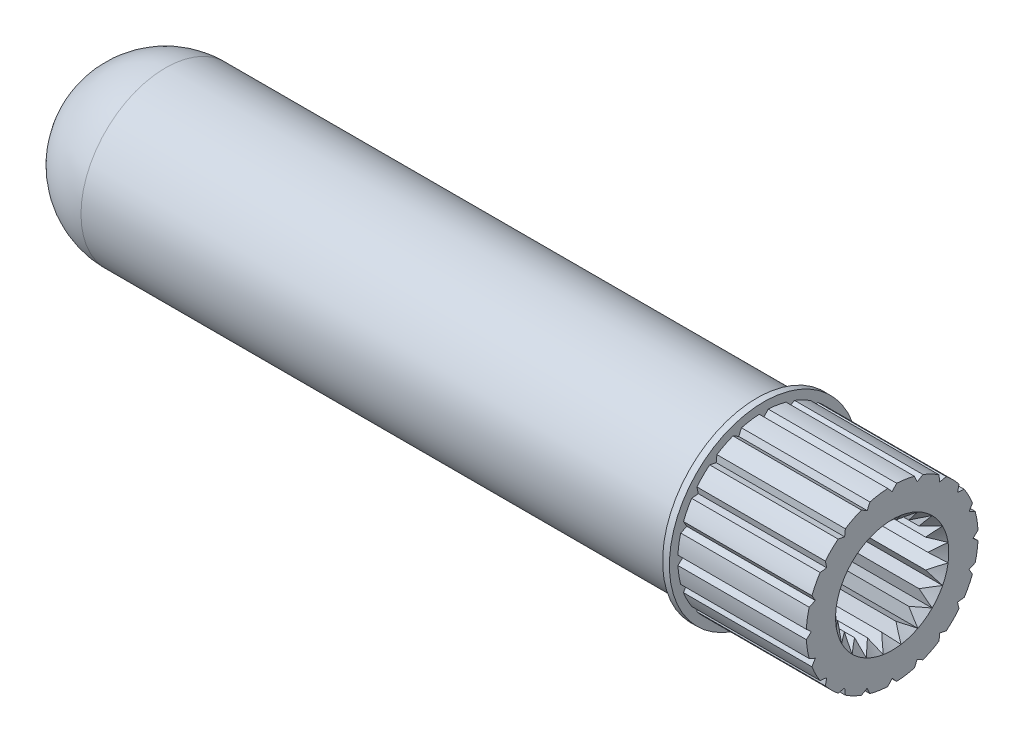
SolidWorks part; units mm, degrees
other "Markup1"
sketch "Sketch46" [suppressed] plane through (18, -9.875, -10) normal (1, 0, 0) x (0, 0, -1)
other "Markup2"
sketch "Sketch47" [suppressed] plane through (18, 5.325, 10) normal (0.9757, 0.2179, 0.0233) x (0.0219, 0.009, -0.9997)
other "DetailItem1"
ref_plane "Front Plane" through (0, 0, 0) normal (0, 0, 1) x (1, 0, 0)
ref_plane "Top Plane" through (0, 0, 0) normal (0, 1, 0) x (1, 0, 0)
ref_plane "Right Plane" through (0, 0, 0) normal (1, 0, 0) x (0, 0, -1)
sketch "Sketch1" plane through (0, 0, 0) normal (0, 1, 0) x (1, 0, 0)
  line L1 (-10, 10) -> (10, 10)
  line L2 (-10, 10) -> (-10, -10)
  line L3 (-10, -10) -> (10, -10)
  line L4 (10, 10) -> (10, -10)
  line L5 (-10, 10) -> (10, -10) construction
  line L6 (-10, -10) -> (10, 10) construction
  point P0 (0, 0)
  dimension "D1" = 20
extrude "Boss-Extrude1" add sketch "Sketch1" along normal blind 5.325 and the other way blind 15.3125
sketch "Sketch2" plane through (0, 0, 0) normal (0, 1, 0) x (1, 0, 0)
  line L0 (0, 0) -> (20, 0)
  dimension "D1" = 20
sketch "Sketch3" plane through (0, 5.325, 0) normal (0, 1, 0) x (1, 0, 0)
  circle A0 centre (0, 0) radius 7.575
  dimension "D1" = 15.15
extrude "Cut-Extrude1" cut sketch "Sketch3" against normal blind 4.3
sketch "Sketch4" plane through (0, 5.325, 0) normal (0, 1, 0) x (1, 0, 0)
  circle A0 centre (0, 0) radius 7
  dimension "D1" = 14
extrude "Cut-Extrude2" cut sketch "Sketch4" against normal blind 12
sketch "Sketch5" plane through (0, 5.325, 0) normal (0, 1, 0) x (1, 0, 0)
  circle A0 centre (0, 0) radius 3.45
  dimension "D1" = 6.9
extrude "Cut-Extrude3" cut sketch "Sketch5" against normal blind 15.2
sketch "Sketch6" plane through (0, 5.325, 0) normal (0, 1, 0) x (1, 0, 0)
  line L4 (10, -10) -> (10, 10)
  line L5 (10, 10) -> (-10, 10)
  line L6 (-10, 10) -> (-10, -10)
  line L7 (-10, -10) -> (10, -10)
  line L8 (10, -10) -> (10, 10)
  line L9 (10, 10) -> (-10, 10)
  line L10 (-10, 10) -> (-10, -10)
  line L11 (-10, -10) -> (10, -10)
  circle A0 centre (0, 0) radius 9 construction
  dimension "D1" = 18
  dimension "D2" = 0
extrude "Cut-Extrude4" cut sketch "Sketch6" against normal through all from offset 15.2 offset against normal yes
sketch "Sketch7" [suppressed] plane through (0, -9.875, 0) normal (0, -1, 0) x (1, 0, 0)
  line L0 (-10, -10) -> (-10, 10) construction
  line L1 (-15.4242, -7.75) -> (-4.5758, -7.75)
  line L2 (-15.4242, -7.75) -> (-15.4242, 7.75)
  line L3 (-15.4242, 7.75) -> (-4.5758, 7.75)
  line L4 (-4.5758, -7.75) -> (-4.5758, 7.75)
  line L5 (-15.4242, -7.75) -> (-4.5758, 7.75) construction
  line L6 (-15.4242, 7.75) -> (-4.5758, -7.75) construction
  circle A0 centre (0, 0) radius 9 construction
  point P0 (-10, 0)
  dimension "D1" = 15.5
extrude "Cut-Extrude7" [suppressed] cut sketch "Sketch7" along normal through all
sketch "Sketch10" plane through (0, -9.875, 0) normal (0, -1, 0) x (1, 0, 0)
  line L1 (-1.4, -7) -> (1.4, -7)
  line L2 (-1.4, -7) -> (-1.4, -9)
  line L3 (-1.4, -9) -> (1.4, -9)
  line L4 (1.4, -7) -> (1.4, -9)
  line L5 (-1.4, -7) -> (1.4, -9) construction
  line L6 (-1.4, -9) -> (1.4, -7) construction
  point P3 (0, -8)
  dimension "D1" = 2.8
  dimension "D2" = 2
  dimension "D3" = 8
extrude "Cut-Extrude9" cut sketch "Sketch10" against normal blind 3
sketch "Sketch15" plane through (0, 5.325, 0) normal (0, 1, 0) x (1, 0, 0)
  line L0 (-6.8653, 3.2013) -> (-7.725, 1.3577)
  line L1 (-7.725, 1.3577) -> (-7.725, -1.3577)
  line L2 (-7.725, -1.3577) -> (-6.8653, -3.2013)
  line L3 (-6.8653, -3.2013) -> (-6.8653, 3.2013)
  circle A0 centre (0, 0) radius 7.575 construction
  circle A1 centre (0, 0) radius 7.575 construction
  point P9 (-7.575, 0)
  dimension "D1" = 25
  dimension "D2" = 0.15
extrude "Cut-Extrude11" cut sketch "Sketch15" against normal up to surface (4.3 mm away) up to face at (0, 1.025, 7)
sketch "Sketch16" plane through (0, -6.675, 0) normal (0, 1, 0) x (1, 0, 0)
  line L0 (-3.1268, 1.458) -> (-3.6, 0.4432)
  line L1 (-3.6, 0.4432) -> (-3.6, -0.4432)
  line L2 (-3.6, -0.4432) -> (-3.1268, -1.458)
  line L3 (-3.1268, -1.458) -> (-3.1268, 1.458)
  circle A0 centre (0, 0) radius 3.45 construction
  point P6 (-3.45, 0)
  dimension "D1" = 0.15
  dimension "D2" = 25
extrude "Cut-Extrude12" cut sketch "Sketch16" against normal up to surface (3.2 mm away) up to face at (0, -9.875, -8)
fillet "Fillet1" radius 10 2 edges at (-10, -2.275, -10) (-10, -2.275, 10)
chamfer "Chamfer5" distance 1 angle 45 4 edges at (5, 5.325, -10) (-7.0711, 5.325, -7.0711) (5, 5.325, 10) (-7.0711, 5.325, 7.0711)
sketch "Sketch18" plane through (10, 0, 0) normal (1, 0, 0) x (0, 0, -1)
  line L0 (-10, -9.875) -> (-10, 4.325) construction
  circle A0 centre (0, 0) radius 10
extrude "Cut-Extrude14" cut sketch "Sketch18" against normal blind 5 flip side to cut
sketch "Sketch19" plane through (5, 0, 0) normal (1, 0, 0) x (0, 0, -1)
  circle A1 centre (0, 0) radius 10
  circle A2 centre (0, 0) radius 10
  dimension "D1" = 0
extrude "Cut-Extrude15" cut sketch "Sketch19" against normal blind 5 draft 60 flip side to cut
sketch "Sketch8" plane through (10, 0, 0) normal (1, 0, 0) x (0, 0, -1)
  circle A0 centre (0, 0) radius 3.35
  dimension "D1" = 6.7
extrude "Start side connector" cut sketch "Sketch8" against normal blind 1.8
sketch "Sketch38" [suppressed] plane through (0, 5.325, 0) normal (0, 1, 0) x (1, 0, 0)
  line L0 (0, -10) -> (10, -10) construction
  line L4 (20, 10) -> (20, -10)
  line L9 (0, 10) -> (0, 15)
  line L10 (0, 15) -> (20, 15)
  line L11 (20, 15) -> (20, 10)
  line L12 (0, -10) -> (0, -15)
  line L13 (0, -15) -> (20, -15)
  line L14 (20, -15) -> (20, -10)
  arc A0 (0, 10) -> (9.5394, -3) centre (0, 0) cw
  arc A1 (0, 10) -> (0, -10) centre (0, 0) ccw construction
  arc A2 (9.5394, -3) -> (0, -10) centre (0, 0) cw
extrude "Cut-Extrude27" [suppressed] cut sketch "Sketch38" against normal through all draft 30
sketch "Sketch9" plane through (10, 0, 0) normal (1, 0, 0) x (0, 0, -1)
  circle A0 centre (0, 0) radius 3.35 construction
  circle A1 centre (0, 0) radius 3.35
  circle A2 centre (0, 0) radius 5.085
  dimension "D1" = 10.17
extrude "Boss-Extrude2" add sketch "Sketch9" along normal blind 8
sketch "Sketch40" plane through (10, 0, 0) normal (1, 0, 0) x (0, 0, -1)
  circle A0 centre (0, 0) radius 5.085 construction
  circle A1 centre (0, 0) radius 5.085
  circle A2 centre (0, 0) radius 5.585
  dimension "D1" = 0.5
extrude "Boss-Extrude10" add sketch "Sketch40" along normal blind 0.4 and the other way blind 1
sketch "Sketch41" [suppressed] plane through (9, 0, 0) normal (-1, 0, 0) x (0, 0, 1)
  line L1 (-1.6842, 5.325) -> (1.6842, 5.325)
  line L2 (-1.6842, 5.325) -> (1.6842, 5.325)
  arc A1 (1.6842, 5.325) -> (-1.6842, 5.325) centre (0, 0) ccw
  arc A2 (1.6842, 5.325) -> (-1.6842, 5.325) centre (0, 0) ccw
  dimension "D1" = 0
extrude "Cut-Extrude28" [suppressed] cut sketch "Sketch41" against normal through all
sketch "Sketch12" plane through (18, 0, 0) normal (1, 0, 0) x (0, 0, -1)
  line L0 (-0.5241, -3.3088) -> (0, -2.73)
  line L1 (0, -2.73) -> (0.5241, -3.3088)
  line L2 (-0.5241, -3.3088) -> (0, 0) construction
  line L3 (0, 0) -> (0.5241, -3.3088) construction
  circle A3 centre (0, 0) radius 3.35 construction
  arc A4 (-0.5241, -3.3088) -> (0.5241, -3.3088) centre (0, 0) ccw
  point P5 (0, -3.35)
  dimension "D1" = 18
  dimension "D2" = 0.62
extrude "Boss-Extrude4" add sketch "Sketch12" against normal up to surface (9.8 mm away) up to face at (8.2, 0, -3.35)
sketch "Sketch17" plane through (18, 0, 0) normal (1, 0, 0) x (0, 0, -1)
  line L0 (-0.2654, -5.0781) -> (0, -4.785)
  line L1 (0, -4.785) -> (0.2654, -5.0781)
  line L2 (0, -2.73) -> (0.5241, -3.3088) construction
  line L3 (-0.5241, -3.3088) -> (0, -2.73) construction
  circle A0 centre (0, 0) radius 5.085 construction
  circle A1 centre (0, 0) radius 5.085 construction
  arc A2 (-0.2654, -5.0781) -> (0.2654, -5.0781) centre (0, 0) ccw
  point P7 (0, -5.085)
  dimension "D1" = 0.3
extrude "Cut-Extrude13" cut sketch "Sketch17" against normal up to surface (7.6 mm away) up to face at (10.4, 0, -5.585)
pattern_circular "CirPattern1" count 20 over 360 about axis through (8.2, 0, 0) along (1, 0, 0) of "Boss-Extrude4", "Cut-Extrude13" reverse direction yes
sketch "Sketch14" plane through (0, 0, 0) normal (0, 1, 0) x (1, 0, 0)
  line L0 (18, 2.35) -> (18, 3.35)
  line L1 (18, -5.085) -> (18, 5.085) construction
  line L2 (18, 3.35) -> (17, 2.35)
  line L3 (17, 2.35) -> (18, 2.35)
  line L8 (10, -3.35) -> (10, 3.35) construction
  point P13 (10, 3.35)
  dimension "D1" = 45
  dimension "D3" = 1
revolve "Cut-Revolve1" cut sketch "Sketch14" angle 360 about L0
fillet "Fillet2" [suppressed] radius 2
chamfer "Chamfer7" [suppressed] distance 4.4 angle 30
sketch "Sketch21" [suppressed] plane through (10, 0, 0) normal (1, 0, 0) x (0, 0, -1)
  circle A0 centre (0, 0) radius 3.55
  circle A1 centre (0, 0) radius 5.15
  dimension "D1" = 7.1
  dimension "D2" = 1.6
extrude "Boss-Extrude5" [suppressed] add sketch "Sketch21" along normal blind 10
sketch "Sketch22" [suppressed] plane through (0, 0, 0) normal (0, 0, 1) x (1, 0, 0)
  line L1 (10, 0) -> (20, 0) construction
  line L2 (10, -5.15) -> (10, 5.15) construction
  line L3 (20, -5.15) -> (20, 5.15) construction
  circle A0 centre (15, 0) radius 1
  dimension "D1" = 2
extrude "Cut-Extrude16" [suppressed] cut sketch "Sketch22" against normal through all both and the other way through all
chamfer "Chamfer3" [suppressed] distance 5 angle 45
sketch "Sketch23" [suppressed] plane through (10, 0, 0) normal (1, 0, 0) x (0, 0, -1)
  circle A0 centre (0, 0) radius 20
  dimension "D1" = 40
extrude "Cut-Extrude17" [suppressed] cut sketch "Sketch23" against normal through all
sketch "Sketch24" [suppressed] plane through (10, 0, 0) normal (-1, 0, 0) x (0, 0, 1)
  circle A0 centre (0, 0) radius 3.55
  circle A1 centre (0, 0) radius 6
  circle A2 centre (0, 0) radius 5.085 construction
  dimension "D1" = 7.1
  dimension "D2" = 2.45
  dimension "D3" = 12
extrude "Boss-Extrude6" [suppressed] add sketch "Sketch24" along normal blind 10
sketch "Sketch26" [suppressed] plane through (10, 0, 0) normal (1, 0, 0) x (0, 0, -1)
  circle A0 centre (0, 0) radius 9
  circle A1 centre (0, 0) radius 6 construction
  circle A2 centre (0, 0) radius 6
  dimension "D1" = 18
extrude "Boss-Extrude7" [suppressed] add sketch "Sketch26" against normal blind 3
chamfer "Chamfer1" [suppressed] distance 3 angle 45
sketch "Sketch25" [suppressed] plane through (0, 0, 0) normal (0, 1, 0) x (1, 0, 0)
  circle A0 centre (4, 0) radius 1
  dimension "D1" = 2
  dimension "D2" = 4
extrude "Cut-Extrude18" [suppressed] cut sketch "Sketch25" against normal through all both and the other way through all
sketch "Sketch43" plane through (10, 0, 0) normal (1, 0, 0) x (0, 0, -1)
  circle A0 centre (0, 0) radius 20
  dimension "D1" = 40
extrude "Cut-Extrude29" cut sketch "Sketch43" against normal through all
sketch "Sketch44" plane through (10, 0, 0) normal (-1, 0, 0) x (0, 0, 1)
  circle A0 centre (0, 0) radius 5
  dimension "D1" = 10
extrude "Boss-Extrude11" add sketch "Sketch44" along normal blind 40
sketch "Sketch45" plane through (10, 0, 0) normal (-1, 0, 0) x (0, 0, 1)
  circle A0 centre (0, 0) radius 9
  dimension "D1" = 18
extrude "Boss-Extrude12" [suppressed] add sketch "Sketch45" along normal blind 3
chamfer "Chamfer4" [suppressed] distance 4 angle 45
fillet "Fillet4" radius 5 1 edges at (-30, 0, 5)
sketch "Sketch27" [suppressed] plane through (10, 0, 0) normal (1, 0, 0) x (0, 0, -1)
  circle A0 centre (0, 0) radius 20
  dimension "D1" = 40
extrude "Cut-Extrude19" [suppressed] cut sketch "Sketch27" against normal through all
sketch "Sketch28" [suppressed] plane through (10, 0, 0) normal (-1, 0, 0) x (0, 0, 1)
  circle A1 centre (0, 0) radius 9
  dimension "D1" = 18
extrude "Boss-Extrude8" [suppressed] add sketch "Sketch28" along normal blind 10
sketch "Sketch29" [suppressed] plane through (10, 0, 0) normal (1, 0, 0) x (0, 0, -1)
  line L40 (-2.2086, 1.6047) -> (-2.9849, 1.5209)
  line L42 (-2.2086, 1.6047) -> (-2.9849, 1.5209)
  line L44 (-2.9849, 1.5209) -> (-2.5964, 0.8436)
  line L46 (-2.9849, 1.5209) -> (-2.5964, 0.8436)
  line L48 (-2.5964, 0.8436) -> (-3.3088, 0.5241)
  line L50 (-2.5964, 0.8436) -> (-3.3088, 0.5241)
  line L52 (-3.3088, 0.5241) -> (-2.73, 0)
  line L54 (-3.3088, 0.5241) -> (-2.73, 0)
  line L56 (-2.73, 0) -> (-3.3088, -0.5241)
  line L58 (-2.73, 0) -> (-3.3088, -0.5241)
  line L60 (-3.3088, -0.5241) -> (-2.5964, -0.8436)
  line L62 (-3.3088, -0.5241) -> (-2.5964, -0.8436)
  line L64 (-2.5964, -0.8436) -> (-2.9849, -1.5209)
  line L66 (-0.5241, -3.3088) -> (0, -2.73)
  line L67 (-0.5241, -3.3088) -> (0, -2.73)
  line L68 (0, -2.73) -> (0.5241, -3.3088)
  line L69 (0, -2.73) -> (0.5241, -3.3088)
  line L70 (-2.5964, -0.8436) -> (-2.9849, -1.5209)
  line L72 (-2.9849, -1.5209) -> (-2.2086, -1.6047)
  line L74 (-2.9849, -1.5209) -> (-2.2086, -1.6047)
  line L76 (-2.2086, -1.6047) -> (-2.3688, -2.3688)
  line L78 (-2.2086, -1.6047) -> (-2.3688, -2.3688)
  line L120 (-2.3688, -2.3688) -> (-1.6047, -2.2086)
  line L122 (-2.3688, -2.3688) -> (-1.6047, -2.2086)
  line L124 (-1.6047, -2.2086) -> (-1.5209, -2.9849)
  line L126 (-1.6047, -2.2086) -> (-1.5209, -2.9849)
  line L128 (-1.5209, -2.9849) -> (-0.8436, -2.5964)
  line L130 (-1.5209, -2.9849) -> (-0.8436, -2.5964)
  line L132 (-0.8436, -2.5964) -> (-0.5241, -3.3088)
  line L134 (-0.8436, -2.5964) -> (-0.5241, -3.3088)
  line L136 (0.5241, -3.3088) -> (0.8436, -2.5964)
  line L138 (0.5241, -3.3088) -> (0.8436, -2.5964)
  line L140 (0.8436, -2.5964) -> (1.5209, -2.9849)
  line L142 (0.8436, -2.5964) -> (1.5209, -2.9849)
  line L144 (1.5209, -2.9849) -> (1.6047, -2.2086)
  line L146 (1.5209, -2.9849) -> (1.6047, -2.2086)
  line L148 (1.6047, -2.2086) -> (2.3688, -2.3688)
  line L150 (1.6047, -2.2086) -> (2.3688, -2.3688)
  line L152 (2.3688, -2.3688) -> (2.2086, -1.6047)
  line L154 (2.3688, -2.3688) -> (2.2086, -1.6047)
  line L156 (2.2086, -1.6047) -> (2.9849, -1.5209)
  line L158 (2.2086, -1.6047) -> (2.9849, -1.5209)
  line L160 (2.9849, -1.5209) -> (2.5964, -0.8436)
  line L161 (2.9849, -1.5209) -> (2.5964, -0.8436)
  line L162 (2.5964, -0.8436) -> (3.3088, -0.5241)
  line L163 (2.5964, -0.8436) -> (3.3088, -0.5241)
  line L164 (3.3088, -0.5241) -> (2.73, 0)
  line L165 (3.3088, -0.5241) -> (2.73, 0)
  line L166 (2.73, 0) -> (3.3088, 0.5241)
  line L167 (2.73, 0) -> (3.3088, 0.5241)
  line L168 (3.3088, 0.5241) -> (2.5964, 0.8436)
  line L169 (3.3088, 0.5241) -> (2.5964, 0.8436)
  line L170 (2.5964, 0.8436) -> (2.9849, 1.5209)
  line L171 (2.5964, 0.8436) -> (2.9849, 1.5209)
  line L172 (2.9849, 1.5209) -> (2.2086, 1.6047)
  line L173 (2.9849, 1.5209) -> (2.2086, 1.6047)
  line L174 (2.2086, 1.6047) -> (2.3688, 2.3688)
  line L175 (2.2086, 1.6047) -> (2.3688, 2.3688)
  line L176 (2.3688, 2.3688) -> (1.6047, 2.2086)
  line L177 (2.3688, 2.3688) -> (1.6047, 2.2086)
  line L178 (1.6047, 2.2086) -> (1.5209, 2.9849)
  line L179 (1.6047, 2.2086) -> (1.5209, 2.9849)
  line L180 (1.5209, 2.9849) -> (0.8436, 2.5964)
  line L181 (1.5209, 2.9849) -> (0.8436, 2.5964)
  line L182 (0.8436, 2.5964) -> (0.5241, 3.3088)
  line L183 (0.8436, 2.5964) -> (0.5241, 3.3088)
  line L184 (0.5241, 3.3088) -> (0, 2.73)
  line L185 (0.5241, 3.3088) -> (0, 2.73)
  line L186 (0, 2.73) -> (-0.5241, 3.3088)
  line L187 (0, 2.73) -> (-0.5241, 3.3088)
  line L188 (-0.5241, 3.3088) -> (-0.8436, 2.5964)
  line L189 (-0.5241, 3.3088) -> (-0.8436, 2.5964)
  line L190 (-0.8436, 2.5964) -> (-1.5209, 2.9849)
  line L191 (-0.8436, 2.5964) -> (-1.5209, 2.9849)
  line L192 (-1.5209, 2.9849) -> (-1.6047, 2.2086)
  line L193 (-1.5209, 2.9849) -> (-1.6047, 2.2086)
  line L194 (-1.6047, 2.2086) -> (-2.3688, 2.3688)
  line L195 (-1.6047, 2.2086) -> (-2.3688, 2.3688)
  line L196 (-2.3688, 2.3688) -> (-2.2086, 1.6047)
  line L197 (-2.3688, 2.3688) -> (-2.2086, 1.6047)
  dimension "D1" = 0
extrude "Cut-Extrude20" [suppressed] cut sketch "Sketch29" against normal blind 1
sketch "Sketch32" [suppressed] plane through (0, 0, 0) normal (0, 1, 0) x (1, 0, 0)
  line L0 (10, -9) -> (10, 9) construction
  circle A0 centre (4.675, 0) radius 3.55
  dimension "D1" = 7.1
  dimension "D2" = 5.325
extrude "Cut-Extrude22" [suppressed] cut sketch "Sketch32" against normal through all and the other way blind 5
sketch "Sketch33" [suppressed] plane through (0, 0, 0) normal (0, 0, 1) x (1, 0, 0)
  line L0 (1.125, 5) -> (8.225, 5) construction
  circle A0 centre (4.675, 0) radius 1.05
  point P4 (4.675, 5)
  dimension "D1" = 2.1
extrude "Cut-Extrude23" [suppressed] cut sketch "Sketch33" against normal through all both and the other way through all
sketch "Sketch34" [suppressed] plane through (10, 0, 0) normal (1, 0, 0) x (0, 0, -1)
  circle A1 centre (0, 0) radius 3.55
  circle A2 centre (0, 0) radius 3.55
  dimension "D1" = 0
extrude "Cut-Extrude24" [suppressed] cut sketch "Sketch34" against normal blind 1
sketch "Sketch35" [suppressed] plane through (0, 0, 0) normal (1, 0, 0) x (0, 0, -1)
  circle A0 centre (0, -2) radius 5
  dimension "D1" = 10
  dimension "D2" = 2
extrude "Boss-Extrude9" [suppressed] add sketch "Sketch35" along normal up to surface (11.3397 mm away) from offset 20 offset against normal yes
sketch "Sketch36" [suppressed] plane through (-20, 0, 0) normal (-1, 0, 0) x (0, 0, 1)
  circle A0 centre (0, -2) radius 1.5
  dimension "D1" = 3
extrude "Cut-Extrude25" [suppressed] cut sketch "Sketch36" against normal blind 10
sketch "Sketch37" [suppressed] plane through (-20, 0, 0) normal (-1, 0, 0) x (0, 0, 1)
  line L1 (-1.6166, -4.8) -> (1.6166, -4.8)
  line L2 (1.6166, -4.8) -> (3.2332, -2)
  line L3 (3.2332, -2) -> (1.6166, 0.8)
  line L4 (1.6166, 0.8) -> (-1.6166, 0.8)
  line L5 (-1.6166, 0.8) -> (-3.2332, -2)
  line L6 (-3.2332, -2) -> (-1.6166, -4.8)
  circle A0 centre (0, -2) radius 2.8 construction
  dimension "D1" = 5.6
extrude "Cut-Extrude26" [suppressed] cut sketch "Sketch37" against normal up to surface (10 mm away) from offset 10 offset against normal yes
chamfer "Chamfer2" [suppressed] distance 2 angle 45
sketch "Sketch42" [suppressed] plane through (0, 5.325, 0) normal (0, 1, 0) x (1, 0, 0)
  circle A1 centre (0, 0) radius 10
  arc A2 (0, 10) -> (-10, 0) centre (0, 0) ccw construction
extrude "Cut 0.2 off of joint" [suppressed] cut sketch "Sketch42" against normal blind 0.2 and the other way through all
fillet "Fillet3" [suppressed] radius 5
chamfer "Chamfer6" [suppressed] distance 1 angle 45
chamfer "Chamfer8" [suppressed] distance 3.4 angle 30
chamfer "Chamfer9" [suppressed] distance 3.3 angle 30
chamfer "Chamfer10" [suppressed] distance 3.5 angle 30
